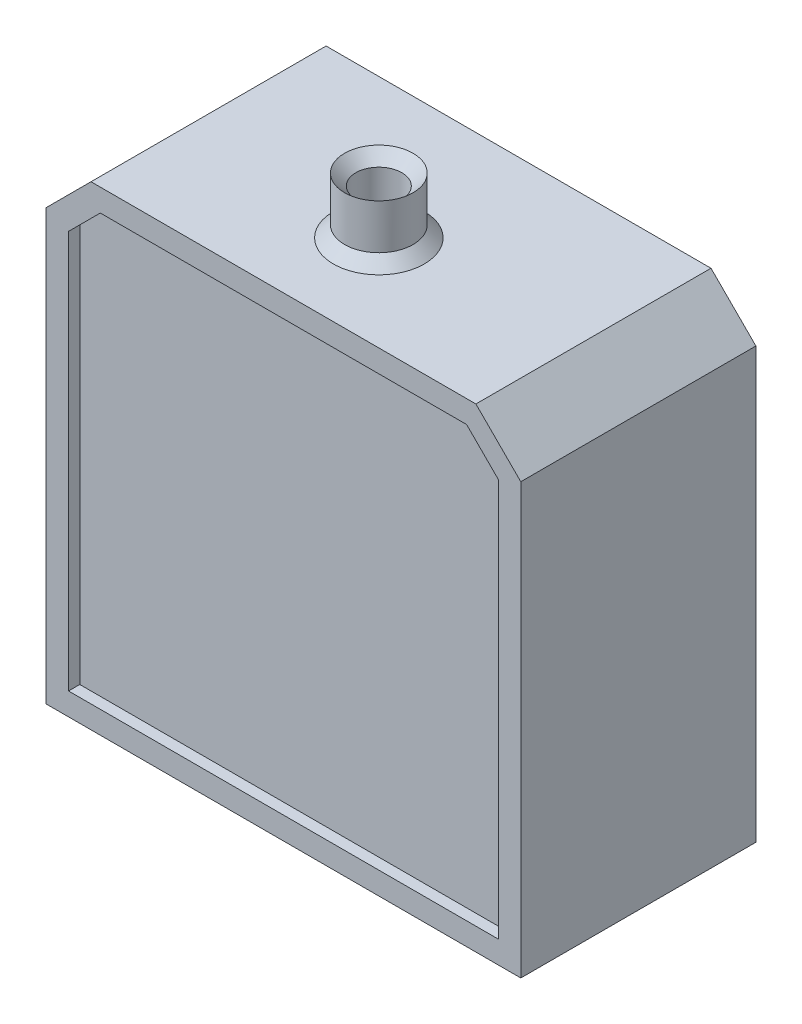
SolidWorks part; units mm, degrees
ref_plane "Front (XY)" through (0, 0, 0) normal (0, 0, 1) x (1, 0, 0)
ref_plane "Top (XZ)" through (0, 0, 0) normal (0, 1, 0) x (1, 0, 0)
ref_plane "Right (YZ)" through (0, 0, 0) normal (1, 0, 0) x (0, 0, -1)
sketch "Sketch3" plane through (0, 0, 0) normal (0, 0, 1) x (1, 0, 0)
  line L0 (21.15, 21.15) -> (21.15, -21.15)
  line L1 (21.15, -21.15) -> (-21.15, -21.15)
  line L2 (-21.15, -21.15) -> (-21.15, 21.15)
  line L3 (-21.15, 21.15) -> (21.15, 21.15)
  point P4 (0, 21.15)
  point P6 (21.15, 0)
  dimension "D1" = 42.3
  dimension "D2" = 42.3
extrude "Boss-Extrude1" add sketch "Sketch3" along normal blind 20.95
sketch "Sketch4" plane through (0, -21.15, 0) normal (0, -1, 0) x (1, 0, 0)
  line L1 (-21.15, 20.95) -> (21.15, 20.95) construction
  line L2 (-21.15, 20.95) -> (-21.15, 0) construction
  circle A0 centre (0, 12.45) radius 4.05
  dimension "D1" = 8.1
  dimension "D2" = 8.5
  dimension "D3" = 21.15
extrude "Cut-Extrude1" cut sketch "Sketch4" against normal blind 5
sketch "Sketch5" plane through (0, 0, 0) normal (0, 0, 1) x (1, 0, 0)
  circle A0 centre (0, 0) radius 2.5
  dimension "D1" = 5
extrude "Cut-Extrude2" cut sketch "Sketch5" along normal blind 8.5
sketch "Sketch6" plane through (0, 21.15, 0) normal (0, 1, 0) x (1, 0, 0)
  circle A2 centre (0, -12.45) radius 3.05
  circle A3 centre (0, -12.45) radius 3.05
  dimension "D1" = 1
extrude "Boss-Extrude2" add sketch "Sketch6" along normal blind 5
sketch "Sketch7" plane through (0, 26.15, 0) normal (0, 1, 0) x (1, 0, 0)
  circle A2 centre (0, -12.45) radius 2.05
  circle A3 centre (0, -12.45) radius 2.05
  dimension "D1" = 1
extrude "Cut-Extrude3" cut sketch "Sketch7" against normal blind 20
chamfer "Chamfer1" distance 4 angle 45 2 edges at (21.15, 21.15, 10.475) (-21.15, 21.15, 10.475)
chamfer "Chamfer3" distance 1 angle 45 2 edges at (0, 26.15, 14.5) (0, 21.15, 9.4)
sketch "Sketch10" plane through (0, 0, 20.95) normal (0, 0, 1) x (1, 0, 0)
  line L12 (19.15, -19.15) -> (19.15, 16.3216)
  line L13 (19.15, 16.3216) -> (16.3216, 19.15)
  line L14 (16.3216, 19.15) -> (-16.3216, 19.15)
  line L15 (-16.3216, 19.15) -> (-19.15, 16.3216)
  line L16 (-19.15, 16.3216) -> (-19.15, -19.15)
  line L17 (-19.15, -19.15) -> (19.15, -19.15)
  line L18 (19.15, -19.15) -> (19.15, 16.3216)
  line L19 (19.15, 16.3216) -> (16.3216, 19.15)
  line L20 (16.3216, 19.15) -> (-16.3216, 19.15)
  line L21 (-16.3216, 19.15) -> (-19.15, 16.3216)
  line L22 (-19.15, 16.3216) -> (-19.15, -19.15)
  line L23 (-19.15, -19.15) -> (19.15, -19.15)
  dimension "D1" = 2
extrude "Cut-Extrude4" cut sketch "Sketch10" against normal blind 1
